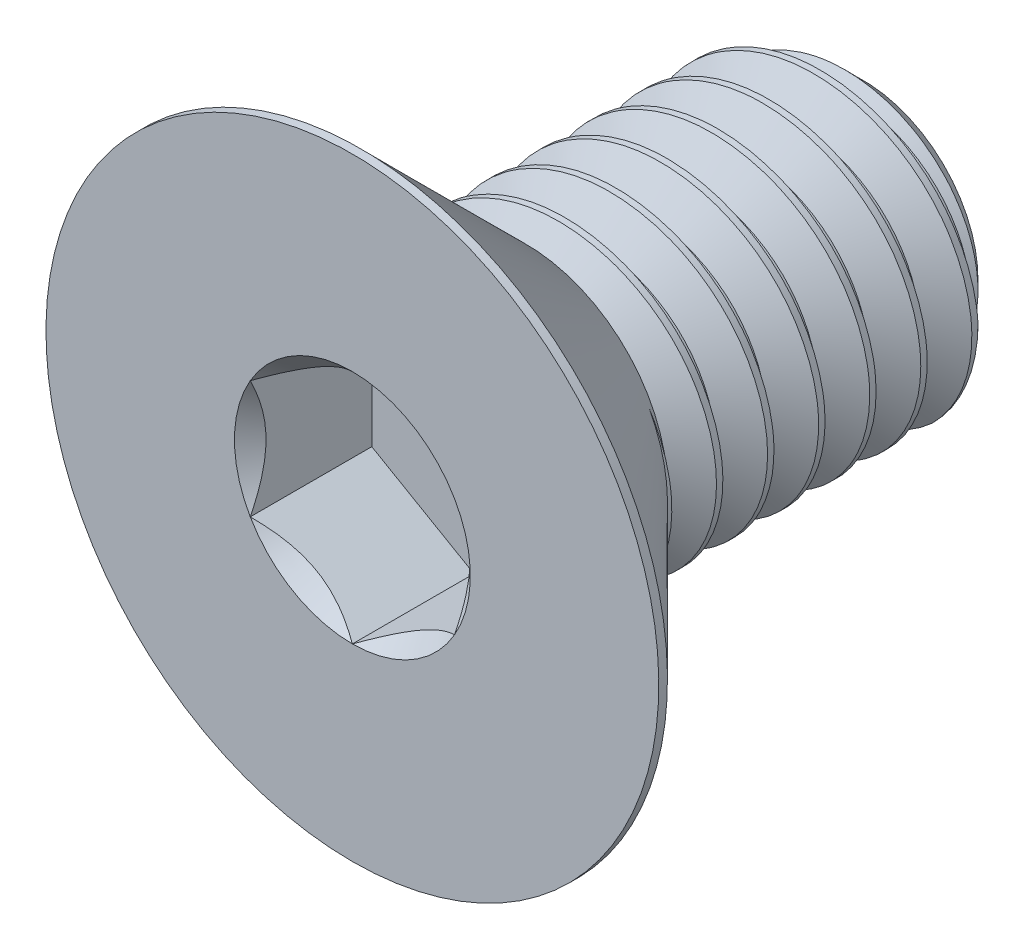
SolidWorks part; units mm, degrees
ref_plane "Front" through (0, 0, 0) normal (0, 0, 1) x (1, 0, 0)
ref_plane "Top" through (0, 0, 0) normal (0, 1, 0) x (1, 0, 0)
ref_plane "Right" through (0, 0, 0) normal (1, 0, 0) x (0, 0, -1)
sketch "Sketch11" plane through (0, 0, 0) normal (1, 0, 0) x (0, 0, -1)
  line L0 (-2.5, 3) -> (2.5, 3) construction
  line L5 (-2.5, 3) -> (-2.5, -3) construction
  line L6 (2.5, 1.5) -> (2.5, -1.5) construction
  line L7 (-2.49, 1) -> (-2.49, -1) construction
  line L8 (2.4688, 1.5541) -> (2.9688, 1.5541) construction
  line L9 (2.9688, 1.5541) -> (2.7188, 1.1211) construction
  line L10 (2.7188, 1.1211) -> (2.4688, 1.5541) construction
  line L11 (2.6875, 1.1752) -> (2.75, 1.1752) construction
  line L12 (2.7188, 1.1752) -> (2.7188, 1.1211) construction
  line L13 (2.4844, 1.5271) -> (2.9531, 1.5271) construction
  line L14 (2.7188, 1.5541) -> (2.7188, 1.5) construction
  line L15 (2.5, 1.5) -> (2.9375, 1.5) construction
  line L17 (-2.415, 3) -> (0.585, 0) construction
  line L18 (0.585, 0) -> (-2.415, -3) construction
  point P3 (-0.8, 3)
  point P8 (0, 3)
  point P21 (2.7188, 1.5271)
  point P26 (-2.5, 0)
  point P28 (-2.49, 0)
  point P29 (2.5, 0)
  dimension "Length" = 5
  dimension "Head Diameter" = 6
  dimension "Thread Major Diameter" = 3
  dimension "Head Height" = 1.7
  dimension "Drive Size" = 2
  dimension "Thread Pitch" = 0.5
  dimension "D1" = 0.0625
  dimension "D2" = 0.01
  dimension "D3" = 0.085
  dimension "Countersink Angle" = 90
sketch "Sketch1" plane through (0, 0, 0) normal (1, 0, 0) x (0, 0, -1)
  line L2 (-0.8, 1.5) -> (2.5, 1.5)
  line L3 (2.5, 1.5) -> (2.5, 0)
  line L4 (-1.31, 1.5) -> (-1.31, 0)
  line L5 (-0.8, 1.5) -> (-1.31, 1.5)
  line L6 (-2.5, 3) -> (-2.5, -3) construction
  line L7 (2.5, 1.5) -> (2.5, -1.5) construction
  line L8 (-1.31, 0) -> (2.5, 0)
  dimension "D1" = 1.19
revolve "Revolve1" add sketch "Sketch1" angle 360 mid plane about L8
chamfer "Chamfer1" distance 0.375 angle 45 1 edges at (0, -1.5, -2.5)
sketch "Sketch7" plane through (0, 0, 0) normal (1, 0, 0) x (0, 0, -1)
  line L2 (-2.5, 3) -> (-2.415, 3)
  line L5 (-0.8, 1.385) -> (-0.8, 0)
  line L6 (-2.5, 3) -> (-2.5, 0)
  line L8 (-2.5, 3) -> (-2.5, -3) construction
  line L9 (-2.5, 0) -> (-0.8, 0)
  line L12 (-2.415, 3) -> (-0.8, 1.385)
  line L13 (-2.415, 3) -> (0.585, 0) construction
revolve "Revolve2" add sketch "Sketch7" angle 360 mid plane about L9 region at (0, 1.1696, 1.7571)
ref_plane "Plane1" through (0, 0, 0.8) normal (0, 0, 1) x (1, 0, 0)
sketch "Sketch5" plane through (0, 0, 2.5) normal (0, 0, 1) x (1, 0, 0)
  line L1 (1, -0.5774) -> (1, 0.5774)
  line L2 (1, 0.5774) -> (0, 1.1547)
  line L3 (0, 1.1547) -> (-1, 0.5774)
  line L4 (-1, 0.5774) -> (-1, -0.5774)
  line L5 (-1, -0.5774) -> (0, -1.1547)
  line L6 (0, -1.1547) -> (1, -0.5774)
  circle A0 centre (0, 0) radius 1 construction
extrude "Cut-Extrude2" cut sketch "Sketch5" against normal blind 1.19
sketch "Sketch6" plane through (0, 0, 2.5) normal (0, 0, -1) x (-1, 0, 0)
  circle A0 centre (0, 0) radius 1.1547
extrude "Cut-Extrude3" cut sketch "Sketch6" along normal blind 1.19 draft 45
sketch "Sketch12" plane through (0, 0, -2.5) normal (0, 0, -1) x (-1, 0, 0)
  circle A0 centre (0, 0) radius 1.5 construction
  circle A1 centre (0, 0) radius 1.5
curve "Helix/Spiral1" pitch 0.5 height 5 radius 1.5 centre (0, 0, -2.5) axis (0, 0, 1) start towards (0, 1, 0)
sketch "Sketch13" plane through (0, 0, 0) normal (1, 0, 0) x (0, 0, -1)
  line L0 (2.4844, 1.5271) -> (2.9531, 1.5271)
  line L1 (2.9531, 1.5271) -> (2.75, 1.1752)
  line L2 (2.75, 1.1752) -> (2.6875, 1.1752)
  line L3 (2.6875, 1.1752) -> (2.4844, 1.5271)
sweep "Cut-Sweep1" cut profiles "Sketch13" path "Helix/Spiral1" align with end faces yes
combine bodies "Combine1" operation type add bodies to combine 113 127
equation "\"D1@Chamfer1\"=\"Thread Pitch@Sketch11\" * .75"
equation "\"D1@Cut-Extrude2\" = \"Head Height@Sketch11\" * .7"
equation "\"D1@Cut-Extrude3\" = \"D1@Cut-Extrude2\""
equation "\"D1@Sketch11\"=\"Thread Pitch@Sketch11\"/8"
equation "\"D3@Sketch11\"=\"Head Height@Sketch11\"*.05"
equation "\"D4@Helix/Spiral1\"=\"Thread Pitch@Sketch11\""
equation "\"D1@Sketch1\"=\"Head Height@Sketch11\"*.7"
equation "\"D3@Helix/Spiral1\"=\"Length@Sketch11\""
